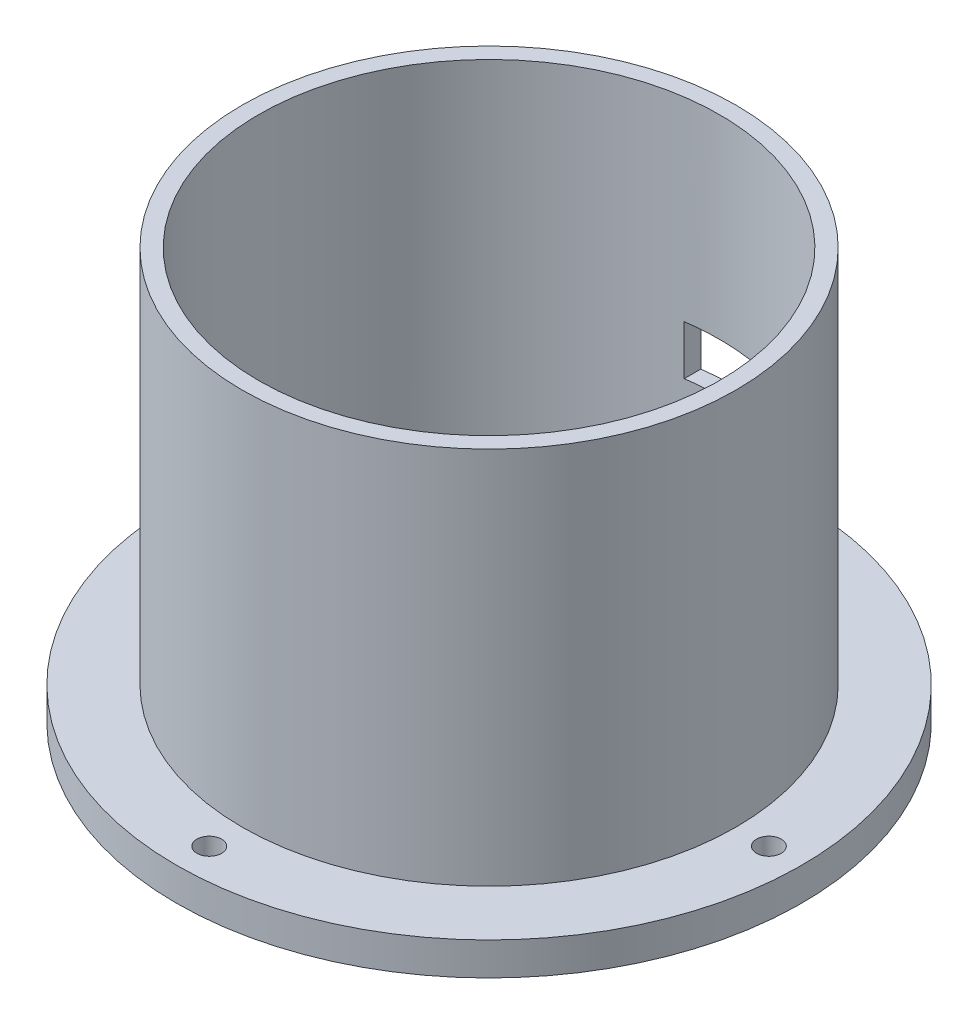
SolidWorks part; units mm, degrees
note: The reader was unsure of these and kept them because the rebuilt part matched: shared geometry of "Sketch2<3>", "Sketch2<4>", "Sketch2<5>".
ref_plane "Płaszczyzna przednia" through (0, 0, 0) normal (0, 0, 1) x (1, 0, 0)
ref_plane "Płaszczyzna górna" through (0, 0, 0) normal (0, 1, 0) x (1, 0, 0)
ref_plane "Płaszczyzna prawa" through (0, 0, 0) normal (1, 0, 0) x (0, 0, -1)
sketch "Sketch2" plane through (0, 0, 0) normal (0, 1, 0) x (1, 0, 0)
  line L0 (-9.6536, -4.1301) -> (-24.8737, -12.9175)
  line L1 (-1.25, 10.4253) -> (1.25, 10.4253)
  line L2 (-1.25, 10.4253) -> (-1.25, 28)
  line L3 (-1.25, 28) -> (1.25, 28)
  line L4 (1.25, 10.4253) -> (1.25, 28)
  line L5 (-8.4036, -6.2952) -> (-23.6237, -15.0825)
  line L6 (-8.4036, -6.2952) -> (-9.6536, -4.1301)
  line L7 (-23.6237, -15.0825) -> (-24.8737, -12.9175)
  line L8 (8.4036, -6.2952) -> (23.6237, -15.0825)
  line L9 (9.6536, -4.1301) -> (24.8737, -12.9175)
  line L10 (9.6536, -4.1301) -> (8.4036, -6.2952)
  line L11 (24.8737, -12.9175) -> (23.6237, -15.0825)
  circle A0 centre (0, 0) radius 5.25
  circle A1 centre (0, 0) radius 10.5
  circle A2 centre (0, 0) radius 28
  circle A3 centre (0, 0) radius 30
  circle A4 centre (0, 0) radius 38
  point P22 (0, 0)
  dimension "D1" = 10.5
  dimension "D2" = 21
  dimension "D3" = 56
  dimension "D5" = 2.5
  dimension "D4" = 2
  dimension "D7" = 8
  dimension "D6" = 3
extrude "Boss-Extrude1" add sketch "Sketch2" along normal blind 3 contours A1 A0 | L6 A1 | L1 A1 | L10 A1
hole_wizard "Ø3.0mm Dowel Hole1" positions "Sketch3" profile "Sketch4" hole size "Ø3.0" standard "ANSI Metric" end condition through all
sketch "Sketch3" plane through (0, 3, 0) normal (0, 1, 0) x (1, 0, 0)
  point P0 (0, 8)
  point P3 (-1.2639, 7.1322)
  point P4 (0, 8.4123)
  dimension "D1" = 8
sketch "Sketch4" plane through (0, 3, -8) normal (1, 0, 0) x (0, 0, 1)
  line L0 (0, 0) -> (0, 3)
  line L1 (0, 3) -> (1.5, 3)
  line L2 (1.5, 3) -> (1.5, 0)
  line L5 (1.5, 0) -> (0, 0)
  line L11 (0, -6.35) -> (0, 107.95) construction
  dimension "Thru Hole Dia." = 3
  dimension "Thru Hole Depth" = 3
pattern_circular "CirPattern1" count 4 over 360 about axis through (0, 0, 0) along (0, 1, 0) of "Ø3.0mm Dowel Hole1"
extrude "Boss-Extrude2" add sketch "Sketch2<3>" along normal blind 50 contours A3 | A2
sketch "Sketch2<3>" plane through (0, 0, 0) normal (0, 1, 0) x (1, 0, 0) same geometry as "Sketch2"
extrude "Boss-Extrude3" add sketch "Sketch2<4>" along normal blind 20 contours L8 A2 L9 A1 | L0 A2 L5 A1 | L4 L3 L2 L1
sketch "Sketch2<4>" plane through (0, 0, 0) normal (0, 1, 0) x (1, 0, 0) same geometry as "Sketch2"
chamfer "Chamfer1" distance 11 angle 57.8 3 edges at (-9.0933, 20, 5.25) (9.0933, 20, 5.25) (0, 20, -10.4253)
extrude "Boss-Extrude4" add sketch "Sketch2<5>" along normal blind 4 contours A4 | A3
sketch "Sketch2<5>" plane through (0, 0, 0) normal (0, 1, 0) x (1, 0, 0) same geometry as "Sketch2"
ref_plane "Plane1" through (0, 0, -30) normal (0, 0, -1) x (0, -1, 0)
sketch "Sketch5" plane through (0, 0, -30) normal (0, 0, -1) x (0, -1, 0)
  line L1 (-26.3456, -4) -> (-20.3456, -4)
  line L2 (-26.3456, -4) -> (-26.3456, 4)
  line L3 (-26.3456, 4) -> (-20.3456, 4)
  line L4 (-20.3456, -4) -> (-20.3456, 4)
  line L7 (0, 0) -> (-62.2372, 0) construction
  dimension "D1" = 6
  dimension "D2" = 8
extrude "Cut-Extrude1" cut sketch "Sketch5" against normal up to next
hole_wizard "Ø3.0 mm Dowel Holes1" positions "Sketch6" profile "Sketch7" hole size "Ø3.0" standard "ANSI Metric"
sketch "Sketch6" plane through (0, 0, 0) normal (0, -1, 0) x (-1, 0, 0)
  circle A0 centre (0, 0) radius 30 construction
  point P0 (34, 0)
  point P3 (34.5474, 0)
  point P4 (0, 0)
  dimension "D1" = 34
sketch "Sketch7" plane through (-34, 0, 0) normal (1, 0, 0) x (0, 0, -1)
  line L0 (0, 0) -> (0, 13.4013)
  line L1 (0, 13.4013) -> (1.5, 12.5)
  line L2 (1.5, 12.5) -> (1.5, 0)
  line L5 (1.5, 0) -> (0, 0)
  line L10 (0, 13.4013) -> (-1.5, 12.5) construction
  line L11 (0, -6.35) -> (0, 107.95) construction
  dimension "Hole Dia." = 3
  dimension "Hole Depth" = 12.5
  dimension "Drill Angle" = 118
pattern_circular "CirPattern2" count 4 over 360 about axis through (0, 0, 0) along (0, 1, 0) of "Ø3.0 mm Dowel Holes1"
